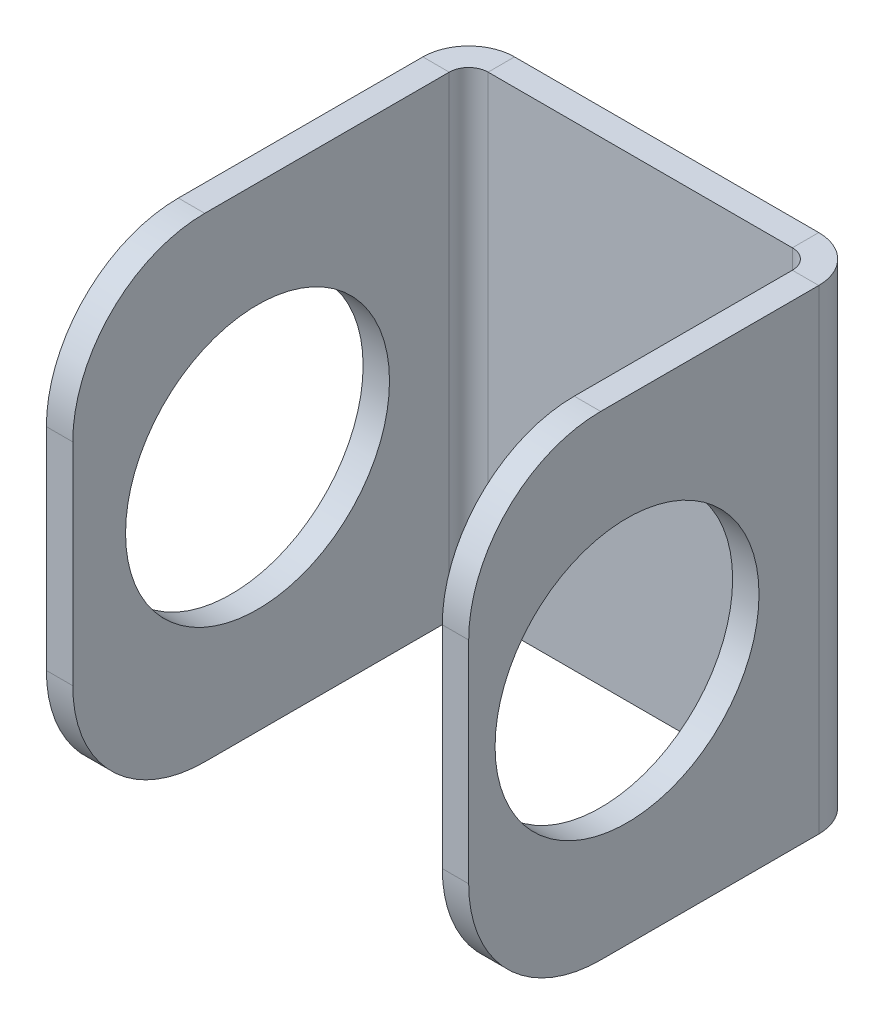
SolidWorks part; units mm, degrees
note: The reader was unsure of these and kept them because the rebuilt part matched: flange length of "Edge-Flange1", "Edge-Flange2".
ref_plane "Front Plane" through (0, 0, 0) normal (0, 0, 1) x (1, 0, 0)
ref_plane "Top Plane" through (0, 0, 0) normal (0, 1, 0) x (1, 0, 0)
ref_plane "Right Plane" through (0, 0, 0) normal (1, 0, 0) x (0, 0, -1)
sketch "Sketch2" plane through (0, 0, 0) normal (0, 0, 1) x (1, 0, 0)
  line L1 (-7.5, -9) -> (7.5, -9)
  line L2 (-7.5, -9) -> (-7.5, 9)
  line L3 (-7.5, 9) -> (7.5, 9)
  line L4 (7.5, -9) -> (7.5, 9)
  line L5 (-7.5, -9) -> (7.5, 9) construction
  line L6 (-7.5, 9) -> (7.5, -9) construction
  point P0 (0, 0)
  dimension "D1" = 15
  dimension "D2" = 18
base flange "Base-Flange1" sketch "Sketch2" thickness 1 reverse thickness direction no parameters "D1"=0.7366
edge flange "Edge-Flange1" sketch "Sketch9" flange angle 90 flange length 15 flange position material inside bend radius 0.7366 thickness 1 relief rectangular parameters "D6"=10
sketch "Sketch9" plane through (7.5, 0, 0) normal (1, 0, 0) x (0, 1, 0)
  line L0 (-9, 0) -> (9, 0) construction
  line L1 (-9, 0) -> (9, 0)
  line L2 (-9, 0) -> (-9, 14)
  line L3 (-9, 14) -> (9, 14)
  line L4 (9, 14) -> (9, 0)
bend "EdgeBend1" bend radius 0.7366 bend angle 90 parameters "D5"=1
edge flange "Edge-Flange2" sketch "Sketch12" flange angle 90 flange length 15 flange position material inside bend radius 0.7366 thickness 1 relief rectangular parameters "D6"=10
sketch "Sketch12" plane through (-7.5, 0, 0) normal (-1, 0, 0) x (0, -1, 0)
  line L0 (-9, 0) -> (9, 0) construction
  line L1 (-9, 0) -> (9, 0)
  line L2 (-9, 0) -> (-9, 15)
  line L3 (-9, 15) -> (9, 15)
  line L4 (9, 15) -> (9, 0)
bend "EdgeBend2" bend radius 0.7366 bend angle 90 parameters "D5"=2
sketch "Sketch13" plane through (-7.5, 0, 0) normal (-1, 0, 0) x (0, 0, 1)
  circle A0 centre (8, 0) radius 5
  dimension "D1" = 10
  dimension "D2" = 8
extrude "Cut-Extrude1" cut sketch "Sketch13" against normal through all normal cut yes
fillet "Fillet1" radius 5 4 edges at (7, 9, 14) (7, -9, 14) (-7, -9, 15) (-7, 9, 15)
sketch "Bend-Lines1" [suppressed] plane through (0, 0, 0) normal (0, 1, 0) x (1, 0, 0)
sketch "Bounding-Box1" [suppressed] plane through (0, 0, 0) normal (0, 1, 0) x (1, 0, 0)
sheet metal parameters "Sheet-Metal1" thickness 1 parameters "D1"=0.7366
flat pattern "Flat-Pattern1" [suppressed]
sketch "Bend-Lines2" plane through (0, 0, 0) normal (0, 1, 0) x (1, 0, 0)
sketch3d "Bounding-Box2" [suppressed]
  line L0 (4, -4, 0) -> (-4, -4, 0) construction
  line L1 (4, 4, 0) -> (-4, 4, 0) construction
  line L2 (4, -4, 0) -> (4, 4, 0) construction
  line L3 (-4, -4, 0) -> (-4, 4, 0) construction
sheet metal parameters "Sheet-Metal2" thickness 1 parameters "D1"=0.7366
flat pattern "Flat-Pattern1"
sketch "Bend-Lines2" plane through (0, 0, 0) normal (0, 0, 1) x (1, 0, 0)
  line L0 (3.2346, -4) -> (3.2346, 4) construction
  line L1 (3.2346, -4) -> (3.2346, 4) construction
sketch3d "Bounding-Box2" [suppressed]
  line L0 (-4, -4, 0) -> (10.4692, -4, 0) construction
  line L1 (-4, 4, 0) -> (10.4692, 4, 0) construction
  line L2 (-4, -4, 0) -> (-4, 4, 0) construction
  line L3 (10.4692, -4, 0) -> (10.4692, 4, 0) construction
bend of the flat pattern "Flatten-<EdgeBend1>1"
sheet metal parameters "Sheet-Metal3" thickness 1 parameters "D1"=0.7366
flat pattern "Flat-Pattern1"
sketch "Bend-Lines2" plane through (0, 0, 0) normal (0, 0, 1) x (1, 0, 0)
  line L0 (6.7346, -9) -> (6.7346, 9) construction
  line L1 (6.7346, -9) -> (6.7346, 9) construction
  line L2 (-6.7346, 9) -> (-6.7346, -9) construction
  line L3 (-6.7346, 9) -> (-6.7346, -9) construction
sketch3d "Bounding-Box2" [suppressed]
  line L0 (-21.9692, -9, 0) -> (20.9692, -9, 0) construction
  line L1 (-21.9692, 9, 0) -> (20.9692, 9, 0) construction
  line L2 (-21.9692, -9, 0) -> (-21.9692, 9, 0) construction
  line L3 (20.9692, -9, 0) -> (20.9692, 9, 0) construction
bend of the flat pattern "Flatten-<EdgeBend1>1"
bend of the flat pattern "Flatten-<EdgeBend2>1"
sheet metal parameters "Sheet-Metal4" thickness 1 parameters "D1"=0.7366
flat pattern "Flat-Pattern1"
sketch "Bend-Lines2" plane through (0, 0, 0) normal (0, 0, 1) x (1, 0, 0)
  line L0 (6.7346, -9) -> (6.7346, 9) construction
  line L1 (6.7346, -9) -> (6.7346, 9) construction
  line L2 (-6.7346, 9) -> (-6.7346, -9) construction
  line L3 (-6.7346, 9) -> (-6.7346, -9) construction
sketch3d "Bounding-Box2" [suppressed]
  line L0 (-21.9692, 9, 0) -> (20.9692, 9, 0) construction
  line L1 (-21.9692, -9, 0) -> (20.9692, -9, 0) construction
  line L2 (-21.9692, 9, 0) -> (-21.9692, -9, 0) construction
  line L3 (20.9692, 9, 0) -> (20.9692, -9, 0) construction
bend of the flat pattern "Flatten-<EdgeBend1>1"
bend of the flat pattern "Flatten-<EdgeBend2>1"
